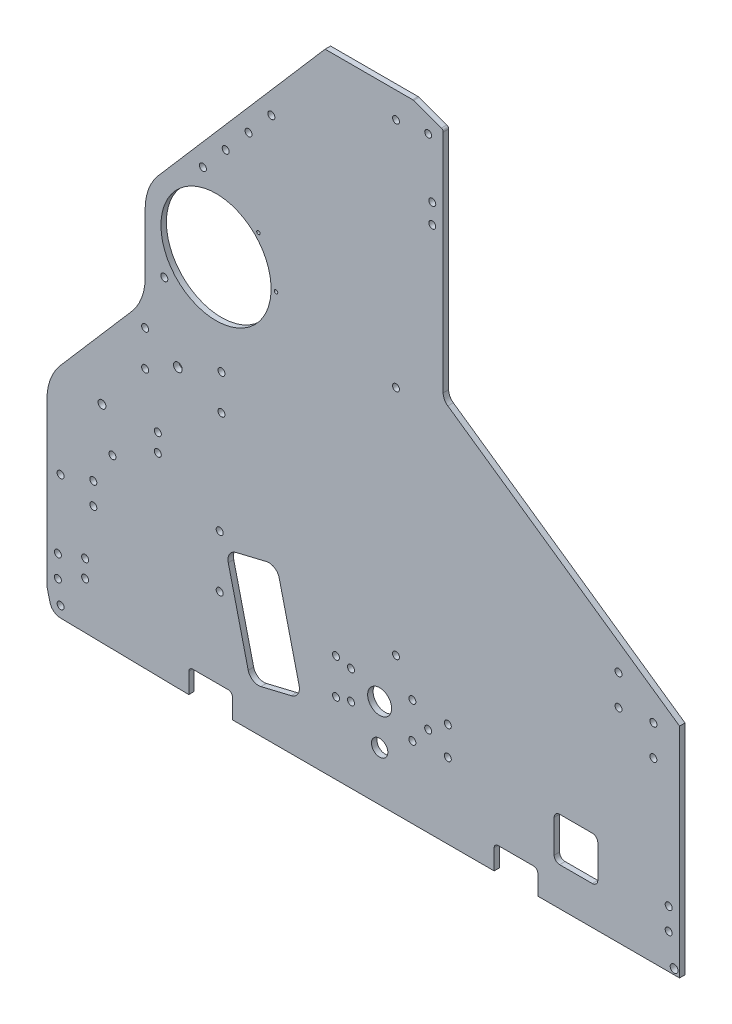
SolidWorks part; units mm, degrees
ref_plane "Front Plane" through (0, 0, 0) normal (0, 0, 1) x (1, 0, 0)
ref_plane "Top Plane" through (0, 0, 0) normal (0, 1, 0) x (1, 0, 0)
ref_plane "Right Plane" through (0, 0, 0) normal (1, 0, 0) x (0, 0, -1)
sketch "Sketch1" plane through (0, 0, 0) normal (0, 0, 1) x (1, 0, 0)
  line L0 (82.55, -20.32) -> (82.55, -6.35)
  line L2 (0, 0) -> (0, 157.48)
  line L4 (368.3, -20.32) -> (368.3, 106.68)
  line L5 (82.55, -6.35) -> (107.95, -6.35)
  line L6 (107.95, -6.35) -> (107.95, -20.32)
  line L7 (107.95, -20.32) -> (260.35, -20.32)
  line L8 (260.35, -20.32) -> (260.35, -6.35)
  line L9 (260.35, -6.35) -> (285.75, -6.35)
  line L10 (285.75, -6.35) -> (285.75, -20.32)
  line L11 (285.75, -20.32) -> (368.3, -20.32)
  line L12 (361.95, 12.7) -> (368.3, 12.7) construction
  line L13 (0, 0) -> (6.35, 0) construction
  line L14 (0.1896, -7.8901) -> (1.7771, -14.2401)
  line L15 (7.8295, -19.0491) -> (82.55, -20.32)
  line L16 (0, 0) -> (0, -6.35)
  line L17 (76.2, 141.605) -> (79.375, 141.605) construction
  line L18 (57.15, 131.2863) -> (101.6, 131.2862) construction
  line L19 (57.15, 131.2863) -> (57.15, 151.9238) construction
  line L20 (101.6, 131.2862) -> (101.6, 151.9237) construction
  line L21 (57.15, 151.9238) -> (101.6, 151.9237) construction
  line L22 (57.15, 131.2863) -> (101.6, 151.9237) construction
  line L23 (101.6, 131.2862) -> (57.15, 151.9238) construction
  line L25 (203.2, 59.805) -> (203.2, 194.805) construction
  line L26 (203.2, 194.805) -> (203.2, 329.805) construction
  line L27 (355.6, 332.105) -> (330.2, 332.105) construction
  line L28 (330.2, 332.105) -> (330.2, 217.805) construction
  line L29 (330.2, 217.805) -> (355.6, 217.805) construction
  line L30 (355.6, 217.805) -> (355.6, 332.105) construction
  line L31 (203.2, 344.805) -> (203.2, 194.805) construction
  line L32 (50.8, 332.105) -> (76.2, 332.105) construction
  line L33 (76.2, 332.105) -> (76.2, 217.805) construction
  line L34 (50.8, 217.805) -> (50.8, 332.105) construction
  line L35 (76.2, 217.805) -> (50.8, 217.805) construction
  line L36 (213.2, 344.805) -> (230.6638, 338.455)
  line L37 (203.2, 344.805) -> (161.925, 344.805)
  line L38 (203.2, 344.805) -> (213.2, 344.805)
  line L39 (348.5362, 344.805) -> (413.4623, 344.805)
  line L40 (348.5362, 344.805) -> (230.6638, 344.805) construction
  line L42 (161.925, 344.805) -> (0, 157.48)
  line L44 (230.6638, 338.455) -> (230.6638, 202.565)
  line L45 (230.6638, 202.565) -> (368.3, 106.68)
  line L46 (213.2, 344.805) -> (-141.0713, 344.805) construction
  circle A0 centre (6.35, 0) radius 2.032
  circle A1 centre (6.35, 12.7) radius 2.032
  circle A2 centre (361.95, 0) radius 2.032
  circle A3 centre (361.95, 12.7) radius 2.032
  arc A5 (1.7771, -14.2401) -> (7.8295, -19.0491) centre (7.9375, -12.7) ccw
  circle A6 centre (7.9375, -12.7) radius 2.032
  arc A7 (0, -6.35) -> (0.1896, -7.8901) centre (6.35, -6.35) ccw
  circle A8 centre (38.1, 78.105) radius 2.032
  circle A9 centre (76.2, 141.605) radius 2.54
  circle A10 centre (101.6, 131.2862) radius 2.032
  circle A11 centre (101.6, 151.9237) radius 2.032
  circle A12 centre (57.15, 151.9238) radius 2.032
  circle A13 centre (57.15, 131.2863) radius 2.032
  circle A15 centre (203.2, 59.805) radius 2
  circle A16 centre (203.2, 194.805) radius 2
  circle A17 centre (203.2, 329.805) radius 2
  circle A18 centre (63.5, 313.055) radius 2.032
  circle A20 centre (355.6, 332.105) radius 2.032
  circle A21 centre (330.2, 332.105) radius 2.032
  circle A22 centre (355.6, 217.805) radius 2.032
  circle A23 centre (330.2, 217.805) radius 2.032
  circle A24 centre (50.8, 332.105) radius 2.032
  circle A25 centre (76.2, 332.105) radius 2.032
  circle A26 centre (50.8, 217.805) radius 2.032
  circle A27 centre (76.2, 217.805) radius 2.032
  circle A28 centre (221.9319, 332.105) radius 2
  circle A29 centre (224.3138, 298.831) radius 2.032
  circle A30 centre (353.06, 100.7351) radius 2.032
  circle A31 centre (332.74, 115.9751) radius 2.032
  circle A32 centre (332.74, 98.1951) radius 2.032
  circle A33 centre (353.06, 82.9551) radius 2.032
  circle A34 centre (117.3562, 280.4276) radius 2.032
  circle A35 centre (104.0678, 265.0548) radius 2.032
  circle A36 centre (90.7795, 249.682) radius 2.032
  circle A38 centre (130.6445, 295.8004) radius 2.032
  circle A39 centre (68.326, 182.9237) radius 2.032
  circle A40 centre (224.3138, 287.401) radius 2.032
  point P82 (203.2, 344.805)
  point P83 (221.9319, 341.63)
  point P90 (368.3, 62.484)
  point P92 (0, 0)
  point P99 (0, 0)
  point P101 (225.766, 282.6312)
  point P103 (224.3138, 282.4895)
  dimension "D6" = 4.064
  dimension "D10" = 6.35
  dimension "D11" = 4.064
  dimension "D17" = 38.1
  dimension "D27" = 4
  dimension "D31" = 4.064
  dimension "D32" = 41.275
  dimension "D36" = 4.064
  dimension "D47" = 39.624
  dimension "D48" = 4.064
  dimension "D25" = 5.08
  dimension "D26" = 4.064
  dimension "D52" = 4.064
  dimension "D65" = 4.064
  dimension "D2" = 127
  dimension "D3" = 13.97
  dimension "D4" = 25.4
  dimension "D5" = 152.4
  dimension "D7" = 12.7
  dimension "D8" = 6.35
  dimension "D9" = 20.32
  dimension "D12" = 12.7
  dimension "D13" = 1.5875
  dimension "D14" = 82.55
  dimension "D15" = 368.3
  dimension "D16" = 6.35
  dimension "D18" = 98.425
  dimension "D19" = 38.1
  dimension "D20" = 63.5
  dimension "D21" = 3.175
  dimension "D22" = 270
  dimension "D23" = 20.6375
  dimension "D24" = 44.45
  dimension "D28" = 135
  dimension "D29" = 12.7
  dimension "D30" = 15
  dimension "D33" = 63.5
  dimension "D34" = 27.4638
  dimension "D35" = 12.7
  dimension "D37" = 114.3
  dimension "D38" = 25.4
  dimension "D39" = 12.7
  dimension "D40" = 157.48
  dimension "D41" = 142.24
  dimension "D42" = 365.125
  dimension "D43" = 10
  dimension "D44" = 6.35
  dimension "D45" = 31.75
  dimension "D46" = 6.35
  dimension "D49" = 6.35
  dimension "D50" = 203.2
  dimension "D51" = 15.24
  dimension "D53" = 17.78
  dimension "D54" = 17.78
  dimension "D55" = 20.32
  dimension "D56" = 15.24
  dimension "D57" = 92.202
  dimension "D58" = 8.382
  dimension "D59" = 20.32
  dimension "D60" = 20.32
  dimension "D61" = 8.382
  dimension "D62" = 20.32
  dimension "D63" = 8.382
  dimension "D64" = 8.382
  dimension "D66" = 35.052
  dimension "D67" = 68.326
  dimension "D68" = 11.43
extrude "Boss-Extrude1" add sketch "Sketch1" along normal blind 3.175 contours L16 A7 L14 A5 L15 L2 A0 A1 A6 region at (171.3489, 119.5243, 0)
fillet "Fillet1" radius 2.286 4 edges at (285.75, -6.35, 1.5875) (107.95, -6.35, 1.5875) (260.35, -6.35, 1.5875) (82.55, -6.35, 1.5875)
fillet "Fillet2" radius 6.35 1 edges at (230.6638, 202.565, 1.5875)
sketch "Sketch2" plane through (0, 0, 0) normal (0, 0, -1) x (-1, 0, 0)
  circle A0 centre (-100.5528, 71.086) radius 2.032 construction
  circle A1 centre (-100.5528, 40.606) radius 2.032 construction
  circle A2 centre (-22.225, 18.2025) radius 2.032 construction
  circle A3 centre (-22.225, 8.0425) radius 2.032 construction
  circle A4 centre (-100.5528, 71.086) radius 2.032
  circle A5 centre (-100.5528, 40.606) radius 2.032
  circle A6 centre (-22.225, 18.2025) radius 2.032
  circle A7 centre (-22.225, 8.0425) radius 2.032
extrude "Cut-Extrude1" cut sketch "Sketch2" against normal through all
fillet "Fillet3" radius 1.5875 2 edges at (230.6638, 338.455, 1.5875) (213.2, 344.805, 1.5875)
sketch "Sketch3" plane through (0, 0, 3.175) normal (0, 0, 1) x (1, 0, 0)
  line L0 (132.9524, 63.2646) -> (132.7215, 64.2281) construction
  line L1 (128.3815, 66.8898) -> (110.6829, 62.6472) construction
  line L2 (114.5132, 58.4237) -> (126.8822, 61.3887) construction
  line L3 (108.0212, 58.3072) -> (108.2522, 57.3436) construction
  line L4 (131.2006, 57.703) -> (140.0164, 20.9266) construction
  line L5 (144.0993, 16.7636) -> (132.9524, 63.2646) construction
  line L6 (108.2522, 57.3436) -> (119.3991, 10.8427) construction
  line L7 (121.1509, 16.4042) -> (112.3351, 53.1807) construction
  line L8 (119.3991, 10.8427) -> (119.6301, 9.8791) construction
  line L9 (144.3303, 15.8001) -> (144.0993, 16.7636) construction
  line L10 (137.8383, 15.6835) -> (125.4694, 12.7185) construction
  line L11 (123.9701, 7.2175) -> (141.6687, 11.4601) construction
  line L12 (132.9524, 63.2646) -> (132.7215, 64.2281)
  line L13 (128.3815, 66.8898) -> (110.6829, 62.6472)
  line L14 (114.5132, 58.4237) -> (126.8822, 61.3887)
  line L15 (108.0212, 58.3072) -> (108.2522, 57.3436)
  line L16 (131.2006, 57.703) -> (140.0164, 20.9266)
  line L17 (144.0993, 16.7636) -> (132.9524, 63.2646)
  line L18 (108.2522, 57.3436) -> (119.3991, 10.8427)
  line L19 (121.1509, 16.4042) -> (112.3351, 53.1807)
  line L20 (119.3991, 10.8427) -> (119.6301, 9.8791)
  line L21 (144.3303, 15.8001) -> (144.0993, 16.7636)
  line L22 (137.8383, 15.6835) -> (125.4694, 12.7185)
  line L23 (123.9701, 7.2175) -> (141.6687, 11.4601)
  line L24 (127.7894, 69.3598) -> (110.0908, 65.1172)
  line L25 (105.5512, 57.7151) -> (105.7822, 56.7515)
  line L26 (105.7822, 56.7515) -> (116.9291, 10.2506)
  line L27 (116.9291, 10.2506) -> (117.16, 9.287)
  line L28 (124.5622, 4.7475) -> (142.2608, 8.9901)
  line L29 (146.8003, 16.3922) -> (146.5694, 17.3557)
  line L30 (146.5694, 17.3557) -> (135.4225, 63.8567)
  line L31 (135.4225, 63.8567) -> (135.1915, 64.8202)
  line L32 (14.605, -0.1369) -> (103.7278, 32.3011) construction
  line L33 (14.605, -0.1369) -> (103.7278, 32.3011)
  line L35 (-39.6666, 74.7152) -> (103.7278, 126.9065) construction
  arc A0 (132.7215, 64.2281) -> (128.6308, 66.9403) centre (129.2206, 63.3889) ccw construction
  arc A1 (110.6829, 62.6472) -> (110.4377, 62.5791) centre (111.522, 59.1463) ccw construction
  arc A2 (128.6308, 66.9403) -> (128.3815, 66.8898) centre (129.2206, 63.3889) ccw construction
  arc A3 (110.4377, 62.5791) -> (108.0212, 58.3072) centre (111.522, 59.1463) ccw construction
  arc A4 (119.6301, 9.8791) -> (123.7207, 7.167) centre (123.1309, 10.7183) ccw construction
  arc A5 (141.9139, 11.5281) -> (144.3303, 15.8001) centre (140.8295, 14.9609) ccw construction
  arc A6 (141.6687, 11.4601) -> (141.9139, 11.5281) centre (140.8295, 14.9609) ccw construction
  arc A7 (123.7207, 7.167) -> (123.9701, 7.2175) centre (123.1309, 10.7183) ccw construction
  arc A8 (132.7215, 64.2281) -> (128.6308, 66.9403) centre (129.2206, 63.3889) ccw
  arc A9 (110.6829, 62.6472) -> (110.4377, 62.5791) centre (111.522, 59.1463) ccw
  arc A10 (128.6308, 66.9403) -> (128.3815, 66.8898) centre (129.2206, 63.3889) ccw
  arc A11 (110.4377, 62.5791) -> (108.0212, 58.3072) centre (111.522, 59.1463) ccw
  arc A12 (119.6301, 9.8791) -> (123.7207, 7.167) centre (123.1309, 10.7183) ccw
  arc A13 (141.9139, 11.5281) -> (144.3303, 15.8001) centre (140.8295, 14.9609) ccw
  arc A14 (141.6687, 11.4601) -> (141.9139, 11.5281) centre (140.8295, 14.9609) ccw
  arc A15 (123.7207, 7.167) -> (123.9701, 7.2175) centre (123.1309, 10.7183) ccw
  arc A16 (110.0908, 65.1172) -> (109.6726, 65.0012) centre (111.522, 59.1463) ccw
  arc A17 (109.6726, 65.0012) -> (105.5512, 57.7151) centre (111.522, 59.1463) ccw
  arc A18 (117.16, 9.287) -> (124.1369, 4.6613) centre (123.1309, 10.7183) ccw
  arc A19 (124.1369, 4.6613) -> (124.5622, 4.7475) centre (123.1309, 10.7183) ccw
  arc A20 (142.2608, 8.9901) -> (142.679, 9.1061) centre (140.8295, 14.9609) ccw
  arc A21 (142.679, 9.1061) -> (146.8003, 16.3922) centre (140.8295, 14.9609) ccw
  arc A22 (135.1915, 64.8202) -> (128.2147, 69.446) centre (129.2206, 63.3889) ccw
  arc A23 (128.2147, 69.446) -> (127.7894, 69.3598) centre (129.2206, 63.3889) ccw
  circle A24 centre (64.5259, 102.9405) radius 2.032 construction
  circle A25 centre (64.5259, 92.5258) radius 2.032 construction
  circle A26 centre (133.35, 208.2281) radius 1.016 construction
  circle A33 centre (26.9875, 46.9531) radius 2.032
  circle A34 centre (26.9875, 59.6531) radius 2.032
  circle A35 centre (7.9375, 53.3031) radius 2.032
  circle A36 centre (7.9375, 53.3031) radius 2.032 construction
  circle A37 centre (32.0306, 100.8109) radius 31.75 construction
  circle A38 centre (32.0306, 100.8109) radius 2.286
  circle A39 centre (123.1207, 232.9238) radius 1.016 construction
  circle A40 centre (64.5259, 102.9405) radius 2.032
  circle A41 centre (64.5259, 92.5258) radius 2.032
  circle A42 centre (133.35, 208.2281) radius 1.016
  circle A43 centre (123.1207, 232.9238) radius 1.016
  circle A44 centre (26.9875, 59.6531) radius 2.032 construction
  circle A45 centre (26.9875, 46.9531) radius 2.032 construction
  ellipse E0 centre (124.5975, 48.8487) end of major axis (128.5376, 61.3578) minor radius 6 (131.2006, 57.703) -> (126.8822, 61.3887) ccw construction
  ellipse E1 centre (122.2349, 48.2824) end of major axis (113.0518, 57.6456) minor radius 6 (114.5132, 58.4237) -> (112.3351, 53.1807) ccw construction
  ellipse E2 centre (127.7541, 25.2585) end of major axis (131.6942, 37.7675) minor radius 6 (121.1509, 16.4042) -> (125.4694, 12.7185) ccw construction
  ellipse E3 centre (130.1166, 25.8248) end of major axis (139.2998, 16.4616) minor radius 6 (137.8383, 15.6835) -> (140.0164, 20.9266) ccw construction
  ellipse E4 centre (124.5975, 48.8487) end of major axis (120.6573, 36.3397) minor radius 6 (131.2006, 57.703) -> (126.8822, 61.3887) ccw
  ellipse E5 centre (122.2349, 48.2824) end of major axis (131.4181, 38.9192) minor radius 6 (114.5132, 58.4237) -> (112.3351, 53.1807) ccw
  ellipse E6 centre (127.7541, 25.2585) end of major axis (131.6942, 37.7675) minor radius 6 (121.1509, 16.4042) -> (125.4694, 12.7185) ccw
  ellipse E7 centre (130.1166, 25.8248) end of major axis (139.2998, 16.4616) minor radius 6 (137.8383, 15.6835) -> (140.0164, 20.9266) ccw
  point P115 (32.0306, 100.8109)
  dimension "D3" = 63.5
  dimension "D4" = 4.572
  dimension "D2" = 88.9
  dimension "D1" = 2.54
extrude "Cut-Extrude2" cut sketch "Sketch3" against normal through all contours A22 A23 L24 A16 A17 L25 L26 L27 A18 A19 L28 A20 A21 L29 L30 L31 A15 A12 L20 L18 L15 A11 A9 L13 A10 A8 L12 L17 L21 A13 A14 L23 | A12 A15 L23 A14 A13 L21 L17 L12 A8 A10 L13 A9 A11 L15 L18 L20 E7 L22 E6 L19 E5 L14 E4 L16 | L22 E7 L16 E4 L14 E5 L19 E6 | A38 | A41 | A40 | A35 | A34 | A33 | A43 | A42 region at (137.844, 39.8506, 3.175) region at (126.1758, 37.0536, 3.175) region at (128.1544, 68.6508, 3.175) region at (32.0306, 100.8109, 3.175) region at (64.5259, 102.9405, 3.175) region at (64.5259, 92.5258, 3.175)
sketch "Sketch4" plane through (0, 0, 3.175) normal (0, 0, 1) x (1, 0, 0)
  line L0 (57.15, 151.9238) -> (101.6, 151.9237) construction
  line L1 (168.275, 21.4312) -> (212.725, 21.4312) construction
  line L2 (168.275, 21.4312) -> (168.275, 42.0687) construction
  line L3 (168.275, 42.0687) -> (212.725, 42.0687) construction
  line L4 (212.725, 21.4312) -> (212.725, 42.0687) construction
  line L5 (168.275, 21.4312) -> (212.725, 42.0687) construction
  line L6 (168.275, 42.0687) -> (212.725, 21.4312) construction
  line L7 (57.15, 131.2863) -> (57.15, 151.9238) construction
  line L8 (107.95, -20.32) -> (260.35, -20.32) construction
  line L9 (193.675, 31.75) -> (177.005, 31.75) construction
  line L10 (190.5, 31.75) -> (193.675, 31.75) construction
  line L11 (6.35, 12.7) -> (361.95, 12.7) construction
  line L12 (107.95, -6.35) -> (107.95, -20.32) construction
  line L13 (193.675, 31.75) -> (220.6625, 31.75) construction
  line L14 (177.005, 23.4569) -> (177.005, 40.0431) construction
  line L15 (213.2, 44.805) -> (193.2, 44.805) construction
  line L16 (213.2, 44.805) -> (213.2, 344.805) construction
  line L17 (213.2, 344.805) -> (193.2, 344.805) construction
  line L18 (193.2, 44.805) -> (193.2, 344.805) construction
  line L19 (213.2, 44.805) -> (193.2, 344.805) construction
  line L20 (213.2, 344.805) -> (193.2, 44.805) construction
  line L21 (226.9319, 332.105) -> (226.9319, 31.75) construction
  line L22 (237.33, 40.0431) -> (233.3612, 40.0431) construction
  line L23 (237.33, 23.4569) -> (233.3612, 23.4569) construction
  circle A0 centre (168.275, 42.0687) radius 2.032
  circle A1 centre (212.725, 42.0687) radius 2.032
  circle A2 centre (212.725, 21.4312) radius 2.032
  circle A3 centre (168.275, 21.4312) radius 2.032
  circle A4 centre (193.675, 31.75) radius 6.985
  circle A7 centre (220.6625, 31.75) radius 14.2875 construction
  circle A8 centre (193.675, 31.75) radius 12.7 construction
  circle A9 centre (177.005, 40.0431) radius 2.032
  circle A10 centre (177.005, 23.4569) radius 2.032
  circle A11 centre (237.33, 40.0431) radius 2.032 construction
  circle A12 centre (237.33, 23.4569) radius 2.032 construction
  circle A13 centre (193.675, 8.4667) radius 4.7625
  circle A14 centre (221.9319, 31.75) radius 2.032
  circle A15 centre (221.9319, 31.75) radius 5 construction
  circle A16 centre (221.9319, 332.105) radius 5 construction
  circle A17 centre (233.3612, 23.4569) radius 2.032
  circle A18 centre (233.3612, 40.0431) radius 2.032
  point P0 (190.5, 31.75)
  point P26 (203.2, 194.805)
  point P38 (177.005, 31.75)
  dimension "D1" = 4.064
  dimension "D4" = 13.97
  dimension "D7" = 9.525
  dimension "D10" = 25.4
  dimension "D11" = 28.575
  dimension "D16" = 10
  dimension "D17" = 4.064
  dimension "D18" = 10
  dimension "D2" = 52.07
  dimension "D3" = 3.175
  dimension "D5" = 82.55
  dimension "D6" = 26.9875
  dimension "D8" = 20
  dimension "D9" = 300
  dimension "D12" = 16.67
  dimension "D13" = 16.5862
  dimension "D14" = 60.325
  dimension "D15" = 23.2833
  dimension "D19" = 3.9688
extrude "Cut-Extrude3" cut sketch "Sketch4" against normal through all
sketch "Sketch5" plane through (0, 0, -187.325) normal (0, 0, -1) x (-1, 0, 0)
  line L0 (-57.15, 223.5947) -> (-57.15, 165.3337)
  line L1 (-161.925, 344.805) -> (-52.7201, 218.4699) construction
  line L2 (-57.15, 165.3337) -> (0, 99.219)
  line L3 (0, -6.35) -> (0, 157.48) construction
  line L4 (-50.4199, 215.8089) -> (0, 157.48) construction
  line L5 (-50.4199, 215.8089) -> (0, 157.48) construction
  line L6 (-57.15, 223.5947) -> (0, 157.48)
  line L7 (0, 157.48) -> (0, 99.219)
  circle A0 centre (-98.425, 208.2281) radius 32.0675
  circle A1 centre (-365.125, -17.145) radius 2.286 construction
  circle A2 centre (-365.125, -17.145) radius 2.286
  dimension "D3" = 64.135
  dimension "D1" = 38.1
  dimension "D2" = 57.15
  dimension "D4" = 41.275
  dimension "D5" = 41.275
extrude "Cut-Extrude5" cut sketch "Sketch5" against normal through all contours A0 | L7 L6 L0 L2 | A2 region at (28.575, 161.4068, -187.325) region at (98.425, 208.2281, -187.325)
fillet "Fillet4" radius 31.75 3 edges at (0, 99.219, 1.5875) (57.15, 165.3337, 1.5875) (57.15, 223.5947, 1.5875)
sketch "Sketch6" plane through (0, 0, 3.175) normal (0, 0, 1) x (1, 0, 0)
  line L0 (285.75, -20.32) -> (368.3, -20.32) construction
  line L1 (298.45, 27.305) -> (317.5, 27.305)
  line L2 (295.275, 24.13) -> (295.275, 5.08)
  line L3 (298.45, 1.905) -> (317.5, 1.905)
  line L4 (320.675, 24.13) -> (320.675, 5.08)
  line L5 (295.275, 27.305) -> (320.675, 1.905) construction
  line L6 (295.275, 1.905) -> (320.675, 27.305) construction
  line L7 (368.3, -20.32) -> (368.3, 106.68) construction
  arc A0 (295.275, 5.08) -> (298.45, 1.905) centre (298.45, 5.08) ccw
  arc A1 (317.5, 1.905) -> (320.675, 5.08) centre (317.5, 5.08) ccw
  arc A2 (317.5, 27.305) -> (320.675, 24.13) centre (317.5, 24.13) cw
  arc A3 (298.45, 27.305) -> (295.275, 24.13) centre (298.45, 24.13) ccw
  point P0 (307.975, 14.605)
  dimension "D2" = 3.175
  dimension "D1" = 25.4
  dimension "D3" = 22.225
  dimension "D4" = 47.625
extrude "Cut-Extrude6" cut sketch "Sketch6" against normal through all
